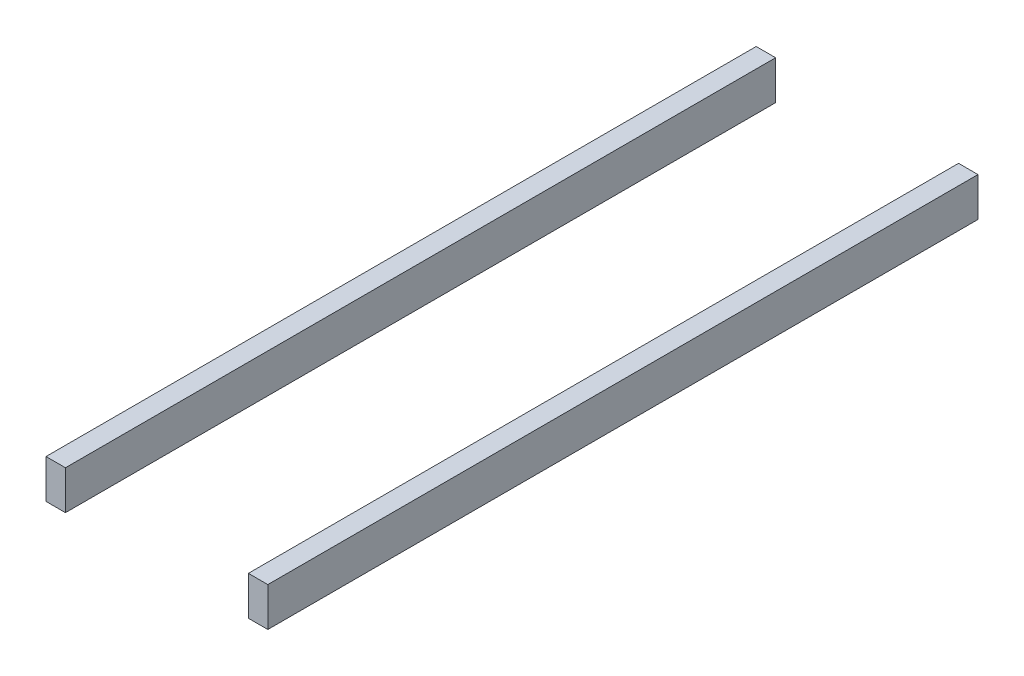
SolidWorks part; units mm, degrees
ref_plane "Front Plane" through (0, 0, 0) normal (0, 0, 1) x (1, 0, 0)
ref_plane "Top Plane" through (0, 0, 0) normal (0, 1, 0) x (1, 0, 0)
ref_plane "Right Plane" through (0, 0, 0) normal (1, 0, 0) x (0, 0, -1)
sketch "Sketch1" plane through (0, 0, 0) normal (0, 1, 0) x (1, 0, 0)
  line L0 (94, 0) -> (-94, 0) construction
  line L1 (94, 365) -> (114, 365)
  line L2 (94, 365) -> (94, -365)
  line L3 (94, -365) -> (114, -365)
  line L4 (114, 365) -> (114, -365)
  line L5 (-94, 365) -> (-114, 365)
  line L6 (-94, 365) -> (-94, -365)
  line L7 (-94, -365) -> (-114, -365)
  line L8 (-114, 365) -> (-114, -365)
  point P9 (-94, 0)
  dimension "D1" = 20
  dimension "D2" = 20
  dimension "D3" = 730
  dimension "D4" = 188
extrude "Boss-Extrude1" add sketch "Sketch1" along normal mid plane 40
